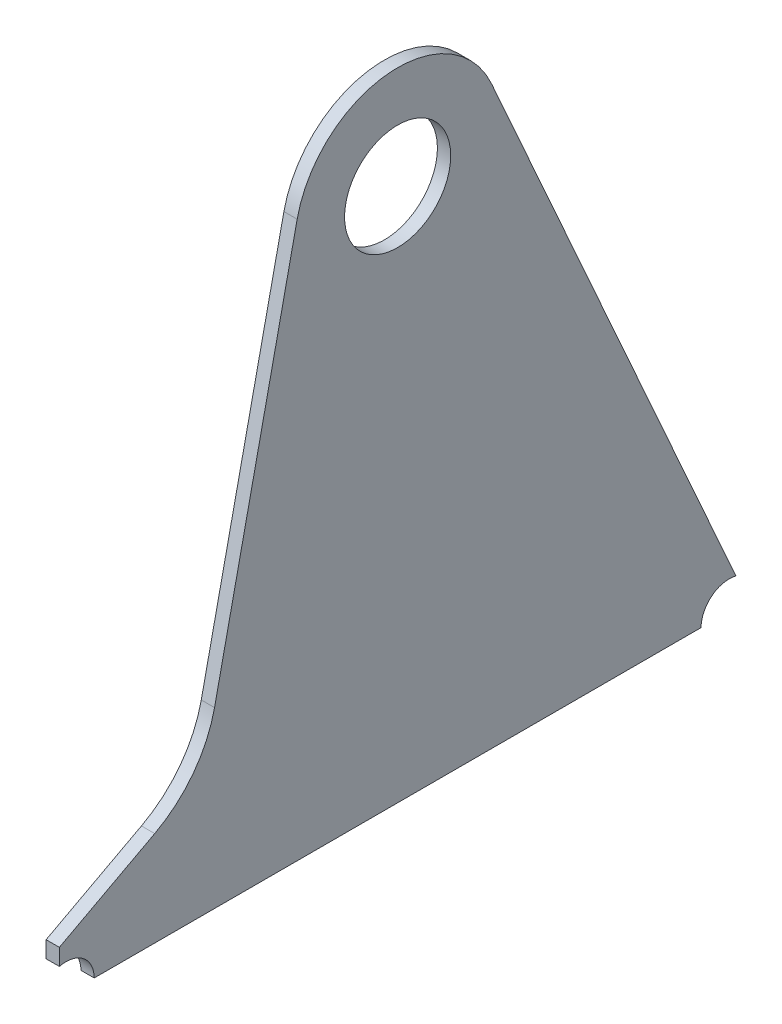
SolidWorks part; units mm, degrees
material "AISI 1020"
ref_plane "Спереди" through (0, 0, 0) normal (0, 0, 1) x (1, 0, 0)
ref_plane "Сверху" through (0, 0, 0) normal (0, 1, 0) x (1, 0, 0)
ref_plane "Справа" through (0, 0, 0) normal (1, 0, 0) x (0, 0, -1)
sketch "Эскиз1" plane through (0, 0, 0) normal (1, 0, 0) x (0, 0, -1)
  line L0 (0, 51.631) -> (0, -161) construction
  line L8 (0, -161) -> (0, -235.9483) construction
  line L12 (-91.5, -161) -> (91.5, -161)
  line L13 (102, -152.7386) -> (28.3159, 12.6178)
  line L14 (-30.2982, 6.559) -> (-55.2129, -108.5307)
  line L15 (-73.2504, -132.4055) -> (-102, -147.7386)
  line L16 (-102, -147.7386) -> (-102, -152.7386)
  line L17 (-114.7059, -148.1765) -> (-75.8824, -127.4706) construction
  circle A0 centre (0, 0) radius 16
  arc A1 (-91.5, -161) -> (-102, -152.7386) centre (-100, -161) ccw
  arc A2 (91.5, -161) -> (102, -152.7386) centre (100, -161) cw
  arc A3 (-30.2982, 6.559) -> (28.3159, 12.6178) centre (0, 0) cw
  arc A7 (-55.2129, -108.5307) -> (-73.2504, -132.4055) centre (-90, -101) cw
  arc A8 (-75.8824, -127.4706) -> (-66.7873, -81.9955) centre (-90, -101) ccw construction
  point P16 (0, -161)
  point P20 (0, -81)
  dimension "D1" = 161
  dimension "D3" = 32
  dimension "D4" = 17
  dimension "D5" = 2
  dimension "D6" = 15
  dimension "D2" = 200
  dimension "D7" = 5
extrude "Бобышка-Вытянуть1" add sketch "Эскиз1" along normal blind 2 and the other way blind 2
